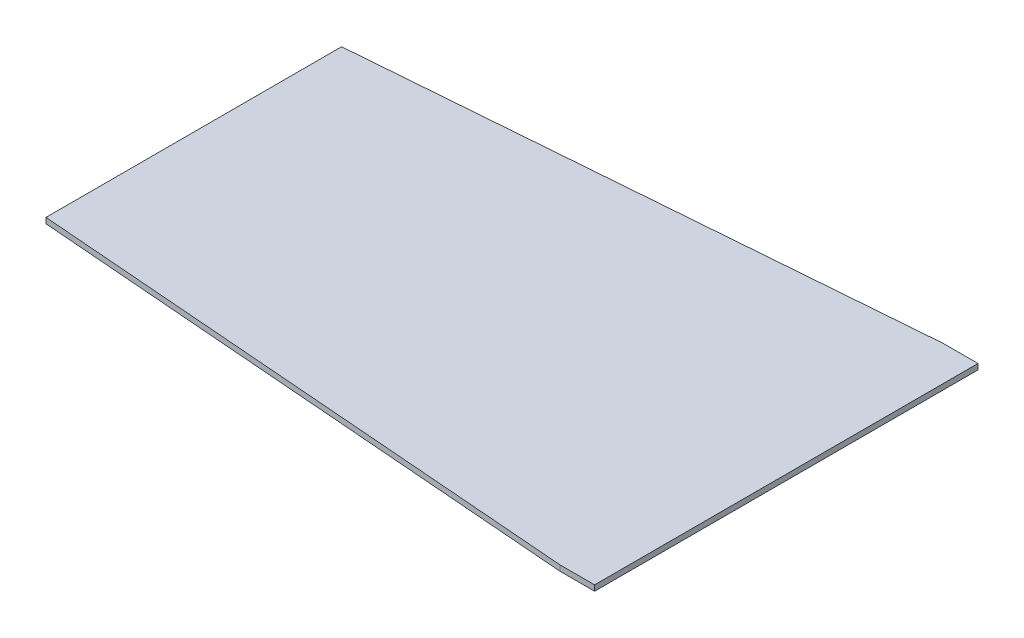
SolidWorks part; units mm, degrees
ref_plane "Front Plane" through (0, 0, 0) normal (0, 0, 1) x (1, 0, 0)
ref_plane "Top Plane" through (0, 0, 0) normal (0, 1, 0) x (1, 0, 0)
ref_plane "Right Plane" through (0, 0, 0) normal (1, 0, 0) x (0, 0, -1)
sketch "Sketch1" plane through (0, 0, 0) normal (0, 1, 0) x (1, 0, 0)
  line L0 (0, -17.4625) -> (0, 17.4625)
  line L1 (0, 17.4625) -> (-3.175, 17.4625)
  line L2 (-3.175, 17.4625) -> (-53.975, 13.462)
  line L3 (-53.975, 13.462) -> (-53.975, -13.462)
  line L4 (-53.975, -13.462) -> (-3.175, -17.4625)
  line L5 (-3.175, -17.4625) -> (0, -17.4625)
  line L6 (0, 0) -> (-77.7732, 0) construction
  dimension "D1" = 53.975
  dimension "D2" = 34.925
  dimension "D3" = 26.924
  dimension "D4" = 3.175
base flange "Base-Flange1" sketch "Sketch1" thickness 0.508 reverse thickness direction no parameters "D1"=0.7366
sketch "Bend-Lines1" plane through (0, 0, 0) normal (0, 1, 0) x (1, 0, 0)
sketch "Bounding-Box1" plane through (0, 0, 0) normal (0, 1, 0) x (1, 0, 0)
sheet metal parameters "Sheet-Metal1" thickness 0.508 parameters "D1"=0.7366
flat pattern "Flat-Pattern1" [suppressed]
sketch "Bend-Lines2" plane through (0, 0, 0) normal (0, 1, 0) x (1, 0, 0)
sketch "Bounding-Box2" [suppressed] plane through (0, 0, 0) normal (0, 1, 0) x (1, 0, 0)
